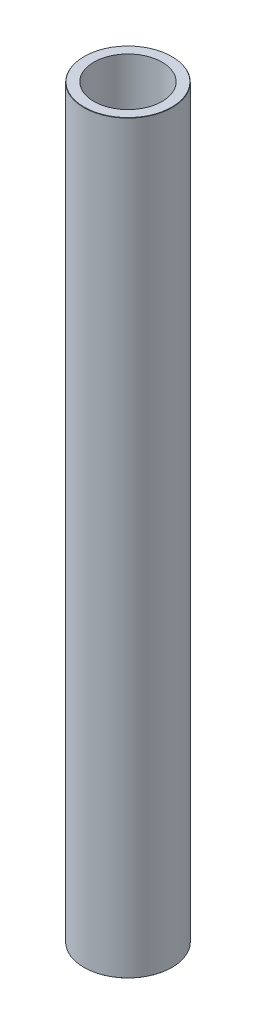
SolidWorks part; units mm, degrees
ref_plane "Front Plane" through (0, 0, 0) normal (0, 0, 1) x (1, 0, 0)
ref_plane "Top Plane" through (0, 0, 0) normal (0, 1, 0) x (1, 0, 0)
ref_plane "Right Plane" through (0, 0, 0) normal (1, 0, 0) x (0, 0, -1)
sketch "Sketch1" plane through (0, 0, 0) normal (0, 1, 0) x (1, 0, 0)
  circle A0 centre (0, 0) radius 32.5
  dimension "SHAFT_OD" = 65
extrude "Boss-Extrude1" add sketch "Sketch1" along normal blind 549.2605
sketch "Sketch2" plane through (0, 0, 0) normal (0, 1, 0) x (1, 0, 0)
  circle A0 centre (0, 0) radius 25.1273
  dimension "BORE_D" = 50.2546
extrude "Cut-Extrude1" cut sketch "Sketch2" along normal through all
chamfer "Chamfer1" distance 0.2179 angle 40.09 2 edges at (0, 549.2605, 32.5) (0, 0, 32.5) first distance on face at (0, 549.2605, 32.5) first distance on face at (0, 0, 25.1273)
